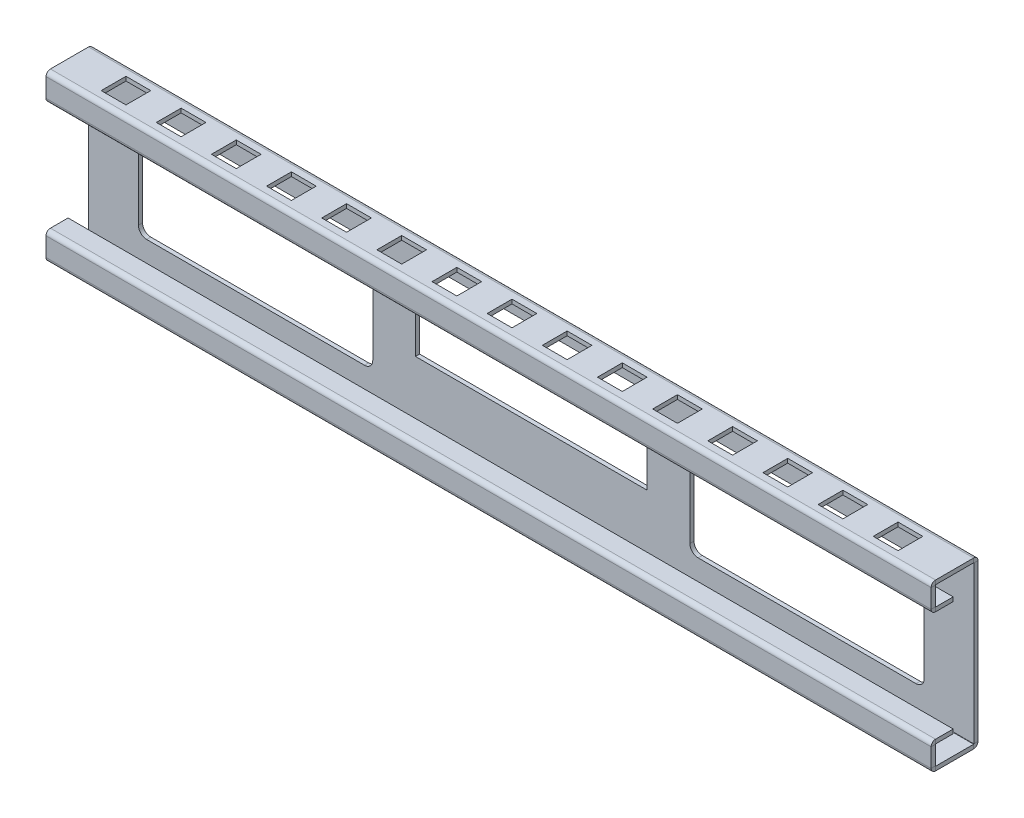
SolidWorks part; units mm, degrees
note: The reader was unsure of these and kept them because the rebuilt part matched: thickness of "基体-法兰1", "边线-法兰1", "边线-法兰2", "边线-法兰3", "钣金6", "钣金7", "钣金8", "钣金9", "钣金13", "钣金16", "钣金17", "钣金18", "钣金19", "钣金20"; flange length of "边线-法兰1", "边线-法兰2", "边线-法兰3".
material "冷轧钢板"
ref_plane "前视基准面" through (0, 0, 0) normal (0, 0, 1) x (1, 0, 0)
ref_plane "上视基准面" through (0, 0, 0) normal (0, 1, 0) x (1, 0, 0)
ref_plane "右视基准面" through (0, 0, 0) normal (1, 0, 0) x (0, 0, -1)
sketch "草图1" plane through (0, 0, 0) normal (0, 0, 1) x (1, 0, 0)
  line L1 (-160.5, 30) -> (160.5, 30)
  line L2 (-160.5, 30) -> (-160.5, -30)
  line L3 (-160.5, -30) -> (160.5, -30)
  line L4 (160.5, 30) -> (160.5, -30)
  line L5 (-160.5, 30) -> (160.5, -30) construction
  line L6 (-160.5, -30) -> (160.5, 30) construction
  point P0 (0, 0)
  dimension "D1" = 321
  dimension "D2" = 60
base flange "基体-法兰1" sketch "草图1" thickness 1.5 reverse thickness direction no parameters "D1"=0.1
edge flange "边线-法兰1" sketch "草图10" flange profiles "草图10", "草图11" flange angle 90 flange length 17 flange position material inside bend radius 0.1 thickness 1.5 parameters "D1"=0.5, "D6"=10, "D8"=1
sketch "草图10" plane through (0, 30, 0) normal (0, 1, 0) x (-1, 0, 0)
  line L2 (-160.5, 0) -> (-160.5, 15.5)
  line L3 (-160.5, 15.5) -> (160.5, 15.5)
  line L4 (160.5, 15.5) -> (160.5, 0)
  line L5 (-160.5, 0) -> (160.5, 0) construction
  line L6 (-160.5, 0) -> (160.5, 0)
sketch "草图11" plane through (0, -30, 0) normal (0, -1, 0) x (1, 0, 0)
  line L0 (-160.5, 0) -> (160.5, 0) construction
  line L1 (-160.5, 0) -> (160.5, 0)
  line L2 (-160.5, 0) -> (-160.5, 15.5)
  line L3 (-160.5, 15.5) -> (160.5, 15.5)
  line L4 (160.5, 15.5) -> (160.5, 0)
bend "边线折弯1" bend radius 0.1 bend angle 90 parameters "D5"=1
bend "边线折弯2" bend radius 0.1 bend angle 90 parameters "D5"=2
edge flange "边线-法兰2" sketch "草图16" flange profiles "草图16", "草图17" flange angle 90 flange length 10 flange position material inside bend radius 0.1 thickness 1.5 parameters "D1"=0.5, "D6"=10, "D8"=1
sketch "草图16" plane through (0, 28.5, 15.5) normal (0, 0, -1) x (1, 0, 0)
  line L1 (160.5, 0) -> (-160.5, 0) construction
  line L2 (-160.5, 0) -> (-160.5, 8.5)
  line L3 (-160.5, 8.5) -> (160.5, 8.5)
  line L4 (160.5, 8.5) -> (160.5, 0)
  line L5 (160.5, 0) -> (-160.5, 0)
sketch "草图17" plane through (0, -28.5, 15.5) normal (0, 0, -1) x (-1, 0, 0)
  line L0 (160.5, 0) -> (-160.5, 0) construction
  line L1 (160.5, 0) -> (-160.5, 0)
  line L2 (160.5, 0) -> (160.5, 8.5)
  line L3 (160.5, 8.5) -> (-160.5, 8.5)
  line L4 (-160.5, 8.5) -> (-160.5, 0)
bend "边线折弯3" bend radius 0.1 bend angle 90 parameters "D5"=3
bend "边线折弯4" bend radius 0.1 bend angle 90 parameters "D5"=4
sketch "草图18" plane through (0, 0, -1.5) normal (0, 0, -1) x (-1, 0, 0)
  line L0 (35.0448, 0) -> (17.959, 0) construction
  line L1 (-39.5, 20) -> (39.5, 20)
  line L2 (-42.5, 17) -> (-42.5, -17)
  line L3 (-39.5, -20) -> (39.5, -20)
  line L4 (42.5, 17) -> (42.5, -17)
  line L5 (-42.5, 20) -> (42.5, -20) construction
  line L6 (-42.5, -20) -> (42.5, 20) construction
  line L7 (160.5, 30) -> (-160.5, 30) construction
  arc A0 (39.5, 20) -> (42.5, 17) centre (39.5, 17) cw
  arc A1 (42.5, -17) -> (39.5, -20) centre (39.5, -17) cw
  arc A2 (-39.5, -20) -> (-42.5, -17) centre (-39.5, -17) cw
  arc A3 (-42.5, 17) -> (-39.5, 20) centre (-39.5, 17) cw
  point P0 (0, 0)
  dimension "D4" = 3
  dimension "D1" = 85
  dimension "D2" = 10
  dimension "D3" = 0
extrude "切除-拉伸1" cut sketch "草图18" against normal blind 10
pattern_linear "阵列(线性)1" count 2 spacing 100 along (-1, 0, 0) count 2 spacing 100 along (1, 0, 0) of "切除-拉伸1"
sketch "草图19" plane through (0, 30, 0) normal (0, 1, 0) x (1, 0, 0)
  line L0 (0, 36.0868) -> (0, -45.539) construction
  line L6 (-160.5, 1.5) -> (160.5, 1.5) construction
  line L7 (-4.5, -2.5) -> (4.5, -2.5)
  line L8 (-4.5, -2.5) -> (-4.5, -11.5)
  line L9 (-4.5, -11.5) -> (4.5, -11.5)
  line L10 (4.5, -2.5) -> (4.5, -11.5)
  line L11 (-4.5, -2.5) -> (4.5, -11.5) construction
  line L12 (-4.5, -11.5) -> (4.5, -2.5) construction
  point P3 (0, -7)
  dimension "D1" = 9
  dimension "D2" = 9
  dimension "D3" = 8.5
extrude "切除-拉伸2" cut sketch "草图19" against normal through all normal cut yes
pattern_linear "阵列(线性)2" count 8 spacing 20 along (-1, 0, 0) count 8 spacing 20 along (1, 0, 0) of "切除-拉伸2"
edge flange "边线-法兰3" sketch "草图24" flange profiles "草图24", "草图25" flange angle 90 flange length 8 flange position material inside bend radius 0.1 thickness 1.5 parameters "D1"=0.5, "D6"=10, "D8"=0.5
sketch "草图24" plane through (0, -20, 14) normal (0, 1, 0) x (1, 0, 0)
  line L0 (-160.5, 0) -> (160.5, 0) construction
  line L1 (-160.5, 0) -> (160.5, 0)
  line L2 (-160.5, 0) -> (-160.5, 6.5)
  line L3 (-160.5, 6.5) -> (160.5, 6.5)
  line L4 (160.5, 6.5) -> (160.5, 0)
sketch "草图25" plane through (0, 20, 14) normal (0, -1, 0) x (-1, 0, 0)
  line L0 (-160.5, 0) -> (160.5, 0) construction
  line L1 (-160.5, 0) -> (160.5, 0)
  line L2 (-160.5, 0) -> (-160.5, 6.5)
  line L3 (-160.5, 6.5) -> (160.5, 6.5)
  line L4 (160.5, 6.5) -> (160.5, 0)
bend "边线折弯5" bend radius 0.1 bend angle 90 parameters "D5"=5
bend "边线折弯6" bend radius 0.1 bend angle 90 parameters "D5"=6
sketch "草图26" plane through (0, 0, -1.5) normal (0, 0, -1) x (-1, 0, 0)
  line L0 (0, 0) -> (0, 73.9374) construction
  line L1 (42.5, -17) -> (42.5, 17) construction
  line L2 (-39.5, -20) -> (39.5, -20) construction
  line L3 (-42.5, 17) -> (-42.5, -17) construction
  line L4 (39.5, 20) -> (-39.5, 20) construction
  line L5 (42.5, -17) -> (42.5, 17)
  line L6 (-39.5, -20) -> (39.5, -20)
  line L7 (-42.5, 17) -> (-42.5, -17)
  line L8 (39.5, 20) -> (-39.5, 20)
  arc A0 (42.5, 17) -> (39.5, 20) centre (39.5, 17) ccw construction
  arc A1 (39.5, -20) -> (42.5, -17) centre (39.5, -17) ccw construction
  arc A2 (-42.5, -17) -> (-39.5, -20) centre (-39.5, -17) ccw construction
  arc A3 (-39.5, 20) -> (-42.5, 17) centre (-39.5, 17) ccw construction
  arc A4 (42.5, 17) -> (39.5, 20) centre (39.5, 17) ccw
  arc A5 (39.5, -20) -> (42.5, -17) centre (39.5, -17) ccw
  arc A6 (-42.5, -17) -> (-39.5, -20) centre (-39.5, -17) ccw
  arc A7 (-39.5, 20) -> (-42.5, 17) centre (-39.5, 17) ccw
extrude "凸台-拉伸1" add sketch "草图26" against normal up to surface (1.5 mm away) up to face at (-100, 0, 0)
sketch "草图27" plane through (0, 0, -1.5) normal (0, 0, -1) x (-1, 0, 0)
  line L0 (0, 0) -> (0, 73.2698) construction
  line L1 (0, 0) -> (90.1268, 0) construction
  line L6 (-42, 23) -> (42, 23)
  line L7 (-42, 23) -> (-42, -8)
  line L8 (-42, -8) -> (42, -8)
  line L9 (42, 23) -> (42, -8)
  line L10 (-42, 23) -> (42, -8) construction
  line L11 (-42, -8) -> (42, 23) construction
  point P3 (0, 7.5)
  dimension "D1" = 84
  dimension "D2" = 31
  dimension "D3" = 8
extrude "切除-拉伸3" cut sketch "草图27" against normal blind 6 normal cut yes
sketch "折弯-线1" [suppressed] plane through (0, 0, 0) normal (0, 1, 0) x (-1, 0, 0)
sketch "边界框1" [suppressed] plane through (0, 0, 0) normal (0, 1, 0) x (-1, 0, 0)
sheet metal parameters "钣金6" thickness 1.5 parameters "D1"=0.1, "D7"=1
flat pattern "平板型式6" [suppressed]
sketch "折弯-线2" plane through (0, 0, 0) normal (0, 1, 0) x (-1, 0, 0)
sketch "边界框2" [suppressed] plane through (0, 0, 0) normal (0, 1, 0) x (-1, 0, 0)
sheet metal parameters "钣金7" thickness 1.5 parameters "D1"=0.1, "D7"=1
flat pattern "平板型式6" [suppressed]
sketch "折弯-线2" plane through (0, 0, 0) normal (0, 1, 0) x (-1, 0, 0)
sketch "边界框2" [suppressed] plane through (0, 0, 0) normal (0, 1, 0) x (-1, 0, 0)
bend of the flat pattern "展开-<边线折弯1>1"
bend of the flat pattern "展开-<边线折弯2>1"
sheet metal parameters "钣金8" thickness 1.5 parameters "D1"=0.1, "D7"=1
flat pattern "平板型式6" [suppressed]
sketch "折弯-线2" plane through (0, 0, 0) normal (0, 1, 0) x (-1, 0, 0)
sketch "边界框2" [suppressed] plane through (0, 0, 0) normal (0, 1, 0) x (-1, 0, 0)
bend of the flat pattern "展开-<边线折弯1>1"
bend of the flat pattern "展开-<边线折弯2>1"
bend of the flat pattern "展开-<边线折弯3>1"
bend of the flat pattern "展开-<边线折弯4>1"
sheet metal parameters "钣金9" thickness 1.5 parameters "D1"=0.1, "D7"=1
flat pattern "平板型式6" [suppressed]
sketch "折弯-线2" plane through (0, 0, 0) normal (0, 1, 0) x (-1, 0, 0)
sketch "边界框2" [suppressed] plane through (0, 0, 0) normal (0, 1, 0) x (-1, 0, 0)
bend of the flat pattern "展开-<边线折弯1>1"
bend of the flat pattern "展开-<边线折弯2>1"
bend of the flat pattern "展开-<边线折弯3>1"
bend of the flat pattern "展开-<边线折弯4>1"
sheet metal parameters "钣金13" thickness 1.5 parameters "D1"=0.1, "D7"=1
flat pattern "平板型式6"
sketch "折弯-线2" plane through (0, 0, 0) normal (0, 0, 1) x (1, 0, 0)
  line L0 (-168, -55.45) -> (168, -55.45) construction
  line L1 (168, 55.45) -> (-168, 55.45) construction
  line L2 (-168, -29.15) -> (168, -29.15) construction
  line L3 (168, 29.15) -> (-168, 29.15) construction
  line L4 (-168, -55.45) -> (168, -55.45) construction
  line L5 (168, 55.45) -> (-168, 55.45) construction
  line L6 (-168, -29.15) -> (168, -29.15) construction
  line L7 (168, 29.15) -> (-168, 29.15) construction
sketch3d "边界框2" [suppressed]
  line L0 (-168, -64.6, 0) -> (168, -64.6, 0) construction
  line L1 (-168, 64.6, 0) -> (168, 64.6, 0) construction
  line L2 (-168, -64.6, 0) -> (-168, 64.6, 0) construction
  line L3 (168, -64.6, 0) -> (168, 64.6, 0) construction
bend of the flat pattern "展开-<边线折弯1>1"
bend of the flat pattern "展开-<边线折弯2>1"
bend of the flat pattern "展开-<边线折弯3>1"
bend of the flat pattern "展开-<边线折弯4>1"
sheet metal parameters "钣金16" thickness 1.5 parameters "D1"=0.1, "D7"=1
flat pattern "平板型式6"
sketch "折弯-线2" plane through (0, 0, 0) normal (0, 0, 1) x (1, 0, 0)
  line L0 (-168, -55.45) -> (168, -55.45) construction
  line L1 (168, 55.45) -> (-168, 55.45) construction
  line L2 (-168, -29.15) -> (168, -29.15) construction
  line L3 (168, 29.15) -> (-168, 29.15) construction
  line L4 (-168, -55.45) -> (168, -55.45) construction
  line L5 (168, 55.45) -> (-168, 55.45) construction
  line L6 (-168, -29.15) -> (168, -29.15) construction
  line L7 (168, 29.15) -> (-168, 29.15) construction
sketch3d "边界框2" [suppressed]
  line L0 (-168, -64.6, 0) -> (168, -64.6, 0) construction
  line L1 (-168, 64.6, 0) -> (168, 64.6, 0) construction
  line L2 (-168, -64.6, 0) -> (-168, 64.6, 0) construction
  line L3 (168, -64.6, 0) -> (168, 64.6, 0) construction
bend of the flat pattern "展开-<边线折弯1>1"
bend of the flat pattern "展开-<边线折弯2>1"
bend of the flat pattern "展开-<边线折弯3>1"
bend of the flat pattern "展开-<边线折弯4>1"
sheet metal parameters "钣金17" thickness 1.5 parameters "D1"=0.1, "D7"=1
flat pattern "平板型式6"
sketch "折弯-线2" plane through (0, 0, 0) normal (0, 0, 1) x (1, 0, 0)
  line L0 (-168, -55.45) -> (168, -55.45) construction
  line L1 (168, 55.45) -> (-168, 55.45) construction
  line L2 (-168, -29.15) -> (168, -29.15) construction
  line L3 (168, 29.15) -> (-168, 29.15) construction
  line L4 (-168, -55.45) -> (168, -55.45) construction
  line L5 (168, 55.45) -> (-168, 55.45) construction
  line L6 (-168, -29.15) -> (168, -29.15) construction
  line L7 (168, 29.15) -> (-168, 29.15) construction
sketch3d "边界框2" [suppressed]
  line L0 (-168, -64.6, 0) -> (168, -64.6, 0) construction
  line L1 (-168, 64.6, 0) -> (168, 64.6, 0) construction
  line L2 (-168, -64.6, 0) -> (-168, 64.6, 0) construction
  line L3 (168, -64.6, 0) -> (168, 64.6, 0) construction
bend of the flat pattern "展开-<边线折弯1>1"
bend of the flat pattern "展开-<边线折弯2>1"
bend of the flat pattern "展开-<边线折弯3>1"
bend of the flat pattern "展开-<边线折弯4>1"
sheet metal parameters "钣金18" thickness 1.5 parameters "D1"=0.1, "D7"=1
flat pattern "平板型式6" [suppressed]
sketch "折弯-线2" plane through (0, 0, 0) normal (0, 0, 1) x (1, 0, 0)
  line L0 (-168, -55.45) -> (168, -55.45) construction
  line L1 (168, 55.45) -> (-168, 55.45) construction
  line L2 (-168, -29.15) -> (168, -29.15) construction
  line L3 (168, 29.15) -> (-168, 29.15) construction
  line L4 (-168, -55.45) -> (168, -55.45) construction
  line L5 (168, 55.45) -> (-168, 55.45) construction
  line L6 (-168, -29.15) -> (168, -29.15) construction
  line L7 (168, 29.15) -> (-168, 29.15) construction
sketch3d "边界框2" [suppressed]
  line L0 (-168, -64.6, 0) -> (168, -64.6, 0) construction
  line L1 (-168, 64.6, 0) -> (168, 64.6, 0) construction
  line L2 (-168, -64.6, 0) -> (-168, 64.6, 0) construction
  line L3 (168, -64.6, 0) -> (168, 64.6, 0) construction
bend of the flat pattern "展开-<边线折弯1>1"
bend of the flat pattern "展开-<边线折弯2>1"
bend of the flat pattern "展开-<边线折弯3>1"
bend of the flat pattern "展开-<边线折弯4>1"
bend of the flat pattern "展开-<边线折弯5>1"
bend of the flat pattern "展开-<边线折弯6>1"
sheet metal parameters "钣金19" thickness 1.5 parameters "D1"=0.1, "D7"=1
flat pattern "平板型式6" [suppressed]
sketch "折弯-线2" plane through (0, 0, 0) normal (0, 0, 1) x (1, 0, 0)
  line L0 (-168, -55.45) -> (168, -55.45) construction
  line L1 (168, 55.45) -> (-168, 55.45) construction
  line L2 (-168, -29.15) -> (168, -29.15) construction
  line L3 (168, 29.15) -> (-168, 29.15) construction
  line L4 (-168, -55.45) -> (168, -55.45) construction
  line L5 (168, 55.45) -> (-168, 55.45) construction
  line L6 (-168, -29.15) -> (168, -29.15) construction
  line L7 (168, 29.15) -> (-168, 29.15) construction
sketch3d "边界框2" [suppressed]
  line L0 (-168, -64.6, 0) -> (168, -64.6, 0) construction
  line L1 (-168, 64.6, 0) -> (168, 64.6, 0) construction
  line L2 (-168, -64.6, 0) -> (-168, 64.6, 0) construction
  line L3 (168, -64.6, 0) -> (168, 64.6, 0) construction
bend of the flat pattern "展开-<边线折弯1>1"
bend of the flat pattern "展开-<边线折弯2>1"
bend of the flat pattern "展开-<边线折弯3>1"
bend of the flat pattern "展开-<边线折弯4>1"
bend of the flat pattern "展开-<边线折弯5>1"
bend of the flat pattern "展开-<边线折弯6>1"
sheet metal parameters "钣金20" thickness 1.5 parameters "D1"=0.1, "D7"=1
flat pattern "平板型式6"
sketch "折弯-线2" plane through (0, 0, 0) normal (0, 0, 1) x (1, 0, 0)
  line L0 (-160.5, -43.25) -> (160.5, -43.25) construction
  line L1 (160.5, 43.25) -> (-160.5, 43.25) construction
  line L2 (-160.5, -28.75) -> (160.5, -28.75) construction
  line L3 (160.5, 28.75) -> (-160.5, 28.75) construction
  line L4 (-160.5, -43.25) -> (160.5, -43.25) construction
  line L5 (160.5, 43.25) -> (-160.5, 43.25) construction
  line L6 (-160.5, -28.75) -> (160.5, -28.75) construction
  line L7 (160.5, 28.75) -> (-160.5, 28.75) construction
  line L8 (160.5, 50.75) -> (-160.5, 50.75) construction
  line L9 (-160.5, -50.75) -> (160.5, -50.75) construction
  line L10 (160.5, 50.75) -> (-160.5, 50.75) construction
  line L11 (-160.5, -50.75) -> (160.5, -50.75) construction
sketch3d "边界框2" [suppressed]
  line L0 (-160.5, -57.5, 0) -> (160.5, -57.5, 0) construction
  line L1 (-160.5, 57.5, 0) -> (160.5, 57.5, 0) construction
  line L2 (-160.5, -57.5, 0) -> (-160.5, 57.5, 0) construction
  line L3 (160.5, -57.5, 0) -> (160.5, 57.5, 0) construction
bend of the flat pattern "展开-<边线折弯1>1"
bend of the flat pattern "展开-<边线折弯2>1"
bend of the flat pattern "展开-<边线折弯3>1"
bend of the flat pattern "展开-<边线折弯4>1"
bend of the flat pattern "展开-<边线折弯5>1"
bend of the flat pattern "展开-<边线折弯6>1"
